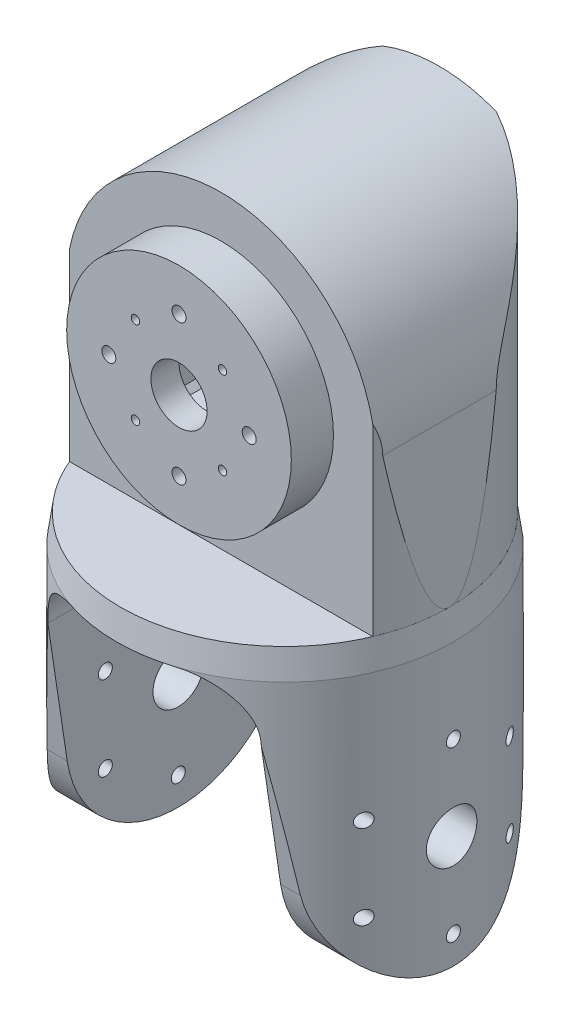
SolidWorks part; units mm, degrees
ref_plane "Front Plane" through (0, 0, 0) normal (0, 0, 1) x (1, 0, 0)
ref_plane "Top Plane" through (0, 0, 0) normal (0, 1, 0) x (1, 0, 0)
ref_plane "Right Plane" through (0, 0, 0) normal (1, 0, 0) x (0, 0, -1)
sketch "Sketch1" plane through (0, 0, 0) normal (0, 1, 0) x (1, 0, 0)
  circle A0 centre (0, 0) radius 60
  point P6 (0, 0)
  dimension "D1" = 120
extrude "Boss-Extrude2" add sketch "Sketch1" along normal blind 40 draft 8
sketch "Sketch3" plane through (0, 0, 0) normal (0, -1, 0) x (1, 0, 0)
  circle A0 centre (0, 0) radius 60
  dimension "D1" = 120
extrude "Boss-Extrude4" add sketch "Sketch3" along normal blind 100
sketch "Sketch4" plane through (0, -100, 0) normal (0, -1, 0) x (1, 0, 0)
  line L1 (38, -46.4327) -> (38, 46.4327)
  line L2 (-38, -46.4327) -> (-38, 46.4327)
  circle A0 centre (0, 0) radius 60 construction
  arc A1 (-38, -46.4327) -> (38, -46.4327) centre (0, 0) ccw
  arc A2 (38, 46.4327) -> (-38, 46.4327) centre (0, 0) ccw
  point P4 (0, 0)
  point P10 (38, 0)
  point P13 (-38, 0)
  dimension "D3" = 60
  dimension "D1" = 76
extrude "Cut-Extrude2" cut sketch "Sketch4" against normal blind 100
fillet "Fillet1" radius 20 2 edges at (38, 0, 0) (-38, 0, 0)
sketch "Sketch5" plane through (-38, 0, 0) normal (1, 0, 0) x (0, 0, -1)
  line L0 (-46.4327, -20) -> (-39.5593, -65.9212)
  line L1 (46.4327, -20) -> (39.5593, -65.9212)
  line L2 (-46.4327, -100) -> (46.4327, -100) construction
  circle A0 centre (0, -60) radius 40
  line M1 (46.4327, -100) -> (46.4327, -20)
  line M3 (-46.4327, -20) -> (-46.4327, -100)
  line M4 (-46.4327, -100) -> (46.4327, -100)
  dimension "D1" = 80
extrude "Cut-Extrude3" cut sketch "Sketch5" against normal blind 80 and the other way blind 200 contours A0 L0 M3 M4 | A0 L1 M4 M1 region at (-38, -79.7558, 37.6248) region at (-38, -79.7558, -37.6248)
sketch "Sketch9" plane through (-38, 0, 0) normal (1, 0, 0) x (0, 0, -1)
  circle A0 centre (0, -60) radius 40
  arc A1 (-39.5593, -65.9212) -> (39.5593, -65.9212) centre (0, -60) ccw construction
  circle A2 centre (0, -60) radius 30
  circle A3 centre (0, -30) radius 2.5
  circle A7 centre (0, -60) radius 9
  circle A8 centre (25.9808, -45) radius 2.5
  circle A9 centre (25.9808, -75) radius 2.5
  circle A10 centre (0, -90) radius 2.5
  circle A11 centre (-25.9808, -75) radius 2.5
  circle A12 centre (-25.9808, -45) radius 2.5
  point P17 (-5, -55)
  point P23 (0, -60)
  dimension "D1" = 80
  dimension "D2" = 60
  dimension "D3" = 5
  dimension "D5" = 18
  dimension "D4" = 6
extrude "Cut-Extrude5" cut sketch "Sketch9" against normal through all both and the other way through all contours A3 | A7 | A8 | A9 | A10 | A11 | A12
sketch "Sketch10" plane through (0, 40, 0) normal (0, 1, 0) x (1, 0, 0)
  circle A0 centre (0, 0) radius 60
  circle A1 centre (0, 0) radius 54.3784 construction
extrude "Cut-Extrude7" cut sketch "Sketch10" against normal blind 30
sketch "Sketch12" plane through (0, 0, 0) normal (0, 0, 1) x (1, 0, 0)
  line L0 (-58.5946, 10) -> (-55, 65)
  line L1 (58.5946, 10) -> (55, 65)
  line L2 (-58.5946, 10) -> (58.5946, 10)
  circle A0 centre (0, 65) radius 55
  dimension "D1" = 110
  dimension "D2" = 65
extrude "Boss-Extrude5" add sketch "Sketch12" along normal mid plane 110 separate body contours A0 | A0 L0 L2 | A0 L2 L1 region at (-44.4966, 23.0845, 0) region at (0, 65, 0) region at (44.4966, 23.0845, 0)
sketch "Sketch13" plane through (0, 10, 0) normal (0, -1, 0) x (1, 0, 0)
  circle A0 centre (0, 0) radius 58.5946
  circle A1 centre (0, 0) radius 58.5946 construction
  circle A2 centre (0, 0) radius 82.5
  dimension "D1" = 165
extrude "Cut-Extrude9" cut sketch "Sketch13" against normal blind 110
sketch "Sketch14" plane through (0, 10, 0) normal (0, 1, 0) x (1, 0, 0)
  line L1 (54, 22.7448) -> (-54, 22.7448)
  line L2 (54, 22.7448) -> (54, -22.7448)
  line L3 (54, -22.7448) -> (-54, -22.7448)
  line L4 (-54, 22.7448) -> (-54, -22.7448)
  line L5 (54, 22.7448) -> (-54, -22.7448) construction
  line L6 (54, -22.7448) -> (-54, 22.7448) construction
  arc A0 (-55, -20.2071) -> (-20.2071, -55) centre (0, 0) ccw construction
  circle A1 centre (0, 0) radius 58.5946
  arc A2 (-20.2071, 55) -> (-55, 20.2071) centre (0, 0) ccw construction
  point P0 (0, 0)
  circle M2 centre (0, 0) radius 58.5946
  dimension "D1" = 108
extrude "Cut-Extrude10" cut sketch "Sketch14" along normal blind 110 contours L3 M2 region at (0, 10, 37.5431)
sketch "Sketch15" plane through (0, 0, 22.7448) normal (0, 0, 1) x (1, 0, 0)
  circle A0 centre (0, 65) radius 40
  arc A1 (54, 75.4403) -> (-54, 75.4403) centre (0, 65) ccw construction
  dimension "D1" = 80
extrude "Boss-Extrude6" add sketch "Sketch15" along normal blind 15
sketch "Sketch16" plane through (0, 0, 37.7448) normal (0, 0, 1) x (1, 0, 0)
  line L1 (-15.5, 80.5) -> (15.5, 80.5) construction
  line L2 (-15.5, 80.5) -> (-15.5, 49.5) construction
  line L3 (-15.5, 49.5) -> (15.5, 49.5) construction
  line L4 (15.5, 80.5) -> (15.5, 49.5) construction
  line L5 (-15.5, 80.5) -> (15.5, 49.5) construction
  line L6 (-15.5, 49.5) -> (15.5, 80.5) construction
  circle A0 centre (0, 65) radius 40 construction
  circle A1 centre (-15.5, 80.5) radius 1.5
  circle A2 centre (15.5, 80.5) radius 1.5
  circle A3 centre (15.5, 49.5) radius 1.5
  circle A4 centre (-15.5, 49.5) radius 1.5
  circle A5 centre (0, 65) radius 10
  point P0 (0, 65)
  dimension "D3" = 3
  dimension "D4" = 20
  dimension "D1" = 31
  dimension "D2" = 31
extrude "Cut-Extrude11" cut sketch "Sketch16" against normal through all
sketch "Sketch17" plane through (0, 0, -55) normal (0, 0, -1) x (-1, 0, 0)
  line L0 (-19, 86) -> (-21, 84)
  line L1 (-19, 86) -> (19, 86)
  line L2 (-21, 84) -> (-21, 46)
  line L3 (-19, 44) -> (19, 44)
  line L4 (21, 84) -> (21, 46)
  line L5 (-21, 86) -> (21, 44) construction
  line L6 (-21, 44) -> (21, 86) construction
  line L7 (19, 86) -> (21, 84)
  line L8 (19, 44) -> (21, 46)
  line L9 (-21, 46) -> (-19, 44)
  point P0 (0, 65)
  dimension "D1" = 42
  dimension "D2" = 42
extrude "Cut-Extrude12" cut sketch "Sketch17" against normal offset from surface (82.7448 mm away) 10 up to face at (-14, 80.5, 37.7448)
sketch "Sketch18" plane through (0, 0, 37.7448) normal (0, 0, 1) x (1, 0, 0)
  circle A0 centre (0, 65) radius 25 construction
  circle A1 centre (0, 90) radius 2.5
  circle A2 centre (25, 65) radius 2.5
  circle A3 centre (0, 40) radius 2.5
  circle A4 centre (-25, 65) radius 2.5
  point P14 (0, 65)
  dimension "D1" = 50
  dimension "D2" = 5
  dimension "D3" = 4
extrude "Cut-Extrude13" cut sketch "Sketch18" against normal through all
